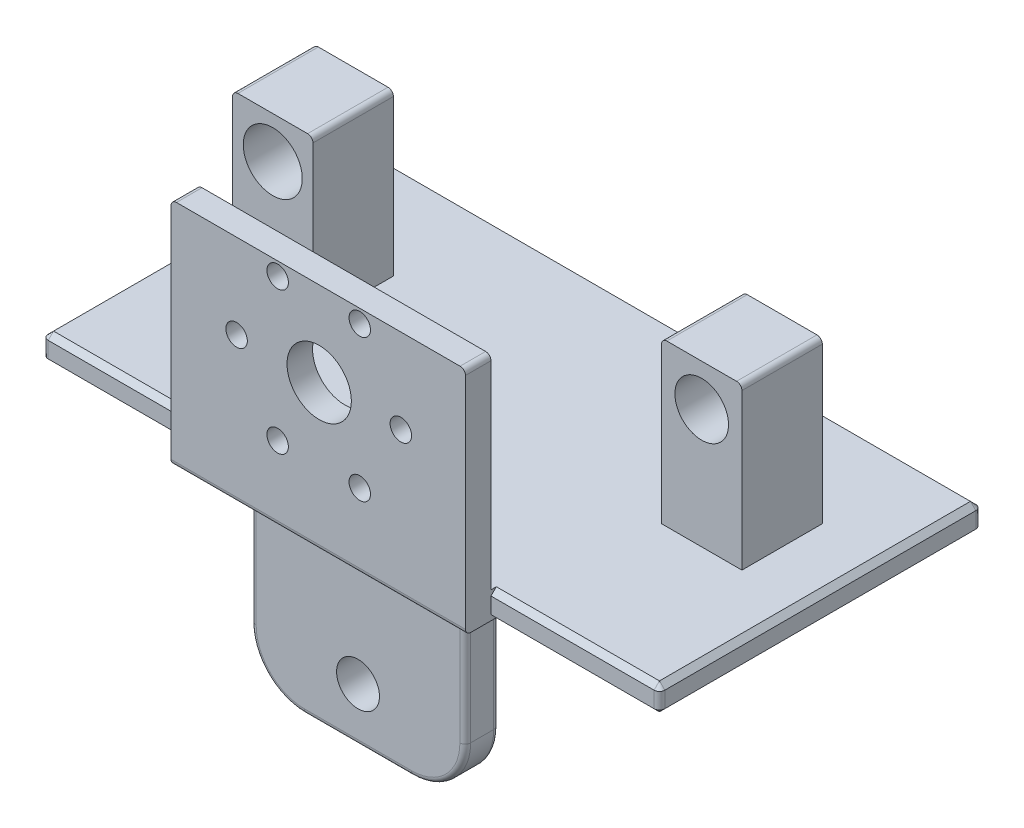
SolidWorks part; units mm, degrees
ref_plane "Alzado" through (0, 0, 0) normal (0, 0, 1) x (1, 0, 0)
ref_plane "Planta" through (0, 0, 0) normal (0, 1, 0) x (1, 0, 0)
ref_plane "Vista lateral" through (0, 0, 0) normal (1, 0, 0) x (0, 0, -1)
sketch "Croquis1" plane through (0, 0, 0) normal (0, 1, 0) x (1, 0, 0)
  line L0 (0, -17.4857) -> (43.5164, -17.4857) construction
  line L5 (75, -36.916) -> (-75, 36.916) construction
  line L6 (75, 36.916) -> (-75, -36.916) construction
  line L7 (43.5164, -17.4857) -> (43.5164, 12.5) construction
  line L8 (-30, 12.5) -> (-45, 12.5)
  line L9 (-30, 12.5) -> (-30, 27.5)
  line L10 (-30, 27.5) -> (-45, 27.5)
  line L11 (-45, 12.5) -> (-45, 27.5)
  line L12 (-30, 12.5) -> (-45, 27.5) construction
  line L13 (-30, 27.5) -> (-45, 12.5) construction
  line L14 (50, 12.5) -> (35, 12.5)
  line L15 (50, 12.5) -> (50, 27.5)
  line L16 (50, 27.5) -> (35, 27.5)
  line L17 (35, 12.5) -> (35, 27.5)
  line L18 (50, 12.5) -> (35, 27.5) construction
  line L19 (50, 27.5) -> (35, 12.5) construction
  point P0 (0, 0)
  point P7 (-37.5, 20)
  point P8 (42.5, 20)
  point P9 (0, 0)
  dimension "D1" = 150
  dimension "D2" = 80
  dimension "D3" = 15
  dimension "D4" = 15
  dimension "D5" = 15
  dimension "D6" = 15
  dimension "D7" = 29.9857
extrude "Saliente-Extruir1" add sketch "Croquis1" along normal blind 30
sketch "Croquis2" plane through (0, 0, -27.5) normal (0, 0, -1) x (-1, 0, 0)
  line L0 (30, 30) -> (30, 0) construction
  circle A0 centre (37.5, 22.2318) radius 5.5
  dimension "D1" = 11
  dimension "D2" = 7.5
extrude "Cortar-Extruir1" cut sketch "Croquis2" against normal blind 30
sketch "Croquis3" plane through (0, 0, -27.5) normal (0, 0, -1) x (-1, 0, 0)
  line L0 (37.5, 22.2318) -> (-42.5, 22.2318) construction
  circle A0 centre (-42.5, 22.2318) radius 5
  dimension "D1" = 10
extrude "Cortar-Extruir2" cut sketch "Croquis3" against normal blind 30
sketch "Croquis5" plane through (0, 0, 0) normal (0, 1, 0) x (1, 0, 0)
  line L5 (-45, 12.5) -> (-53.8007, -14.0809) construction
  line L6 (-53.8007, -14.0809) -> (-53.8007, 45.9191)
  line L7 (-53.8007, 45.9191) -> (61.1993, 45.9191)
  line L8 (61.1993, 45.9191) -> (61.1993, -14.0809)
  line L9 (61.1993, -14.0809) -> (-53.8007, -14.0809)
  dimension "D1" = 28
  dimension "D2" = 60
  dimension "D3" = 115
extrude "Saliente-Extruir3" add sketch "Croquis5" against normal blind 5
sketch "Croquis6" plane through (0, 0, 14.0809) normal (0, 0, 1) x (1, 0, 0)
  line L0 (-53.8007, -5) -> (61.1993, -5) construction
  line L1 (-25.119, -5) -> (29.7791, -5)
  line L2 (-25.119, -5) -> (-25.119, 38)
  line L3 (-25.119, 38) -> (29.7791, 38)
  line L4 (29.7791, -5) -> (29.7791, 38)
  dimension "D1" = 43
extrude "Saliente-Extruir4" add sketch "Croquis6" along normal blind 4.7625
ref_point "Punto1"
ref_axis "Eje1" through (2.3301, 16.5, 18.8434) along (0, 0, 1)
sketch "Croquis7" plane through (0, 0, 18.8434) normal (0, 0, 1) x (1, 0, 0)
  line L0 (-25.119, -5) -> (29.7791, -5) construction
  circle A0 centre (17.7301, 22.23) radius 2
  circle A2 centre (10.0719, 8.9656) radius 2
  circle A3 centre (-5.2445, 8.9656) radius 2
  circle A4 centre (-12.9027, 22.23) radius 2
  circle A5 centre (-5.2445, 35.4944) radius 2
  circle A6 centre (10.0719, 35.4944) radius 2
  point P5 (2.4137, 22.23)
  point P19 (2.4137, 22.23)
  dimension "D1" = 27.23
  dimension "D3" = 4
  dimension "D2" = 15.4
  dimension "D4" = 6
extrude "Cortar-Extruir3" cut sketch "Croquis7" against normal blind 4.7625
sketch "Croquis8" plane through (0, 0, 18.8434) normal (0, 0, 1) x (1, 0, 0)
  line L0 (-37.5, 22.2318) -> (42.5, 22.2318) construction
  circle A0 centre (2.5, 22.2318) radius 6
  dimension "D1" = 12
extrude "Cortar-Extruir4" cut sketch "Croquis8" against normal blind 10
sketch "Croquis9" plane through (0, -5, 0) normal (0, -1, 0) x (-1, 0, 0)
  line L0 (-2.6005, 12.6005) -> (-2.6005, 30.6005) construction
  line L5 (-2.6005, -5.3995) -> (-2.6005, 12.6005) construction
  line L9 (17.3995, 36.9005) -> (-22.6005, 36.9005)
  line L10 (17.3995, -5.3995) -> (-22.6005, -5.3995)
  line L11 (17.3995, -5.3995) -> (17.3995, -11.6995)
  line L12 (17.3995, -11.6995) -> (-22.6005, -11.6995)
  line L13 (-22.6005, -5.3995) -> (-22.6005, -11.6995)
  line L14 (-22.6005, 30.6005) -> (-22.6005, 36.9005)
  line L15 (17.3995, 30.6005) -> (-22.6005, 30.6005)
  line L16 (17.3995, 30.6005) -> (17.3995, 36.9005)
  point P11 (-2.6005, 12.6005)
  dimension "D1" = 40
  dimension "D2" = 40
  dimension "D3" = 18
  dimension "D4" = 6.3
  dimension "D5" = 6.3
  dimension "D6" = 18
extrude "Saliente-Extruir5" add sketch "Croquis9" along normal blind 35
fillet "Redondeo1" radius 10 4 edges at (22.6005, -40, -33.7505) (-17.3995, -40, -33.7505) (22.6005, -40, 8.5495) (-17.3995, -40, 8.5495)
sketch "Croquis10" plane through (0, 0, 11.6995) normal (0, 0, 1) x (1, 0, 0)
  line L0 (2.6005, -5) -> (2.6005, -30) construction
  line L1 (22.6005, -5) -> (-17.3995, -5) construction
  circle A0 centre (2.6005, -30) radius 4
  dimension "D1" = 8
  dimension "D2" = 25
extrude "Cortar-Extruir5" cut sketch "Croquis10" against normal up to surface (48.6 mm away) up to face at (2.6005, -25.6904, -36.9005)
fillet "Redondeo3" radius 1 20 edges at (-17.3995, -17.5, 11.6995) (-14.4706, -37.0711, 11.6995) (2.6005, -40, 11.6995) (19.6716, -37.0711, 11.6995) (22.6005, -17.5, 11.6995) (22.6005, -17.5, 5.3995) (19.6716, -37.0711, 5.3995) (2.6005, -40, 5.3995) (-14.4706, -37.0711, 5.3995) (-17.3995, -17.5, 5.3995) (-17.3995, -17.5, -30.6005) (-14.4706, -37.0711, -30.6005) (2.6005, -40, -30.6005) (19.6716, -37.0711, -30.6005) (22.6005, -17.5, -30.6005) (22.6005, -17.5, -36.9005) (-17.3995, -17.5, -36.9005) (-14.4706, -37.0711, -36.9005) (2.6005, -40, -36.9005) (19.6716, -37.0711, -36.9005)
fillet "Redondeo4" radius 1 4 edges at (61.1993, -2.5, 14.0809) (-53.8007, -2.5, 14.0809) (-53.8007, -2.5, -45.9191) (61.1993, -2.5, -45.9191)
fillet "Redondeo5" radius 1 4 edges at (-45, 30, -20) (-30, 30, -20) (35, 30, -20) (50, 30, -20)
fillet "Redondeo6" radius 1 2 edges at (-25.119, 38, 16.4622) (29.7791, 38, 16.4622)
fillet "Redondeo8" radius 1 1 edges at (2.3301, -5, 18.8434)
chamfer "Chaflán1" distance 1 angle 45 18 edges at (-38.9599, 0, 14.0809) (-53.5079, 0, 13.7881) (-53.8007, 0, -15.9191) (-53.5079, 0, -45.6262) (44.9892, 0, 14.0809) (3.6993, 0, -45.9191) (60.9064, 0, 13.7881) (60.9064, 0, -45.6262) (61.1993, 0, -15.9191) (44.9892, -5, 14.0809) (-38.9599, -5, 14.0809) (60.9064, -5, 13.7881) (-53.5079, -5, 13.7881) (61.1993, -5, -15.9191) (-53.8007, -5, -15.9191) (60.9064, -5, -45.6262) (-53.5079, -5, -45.6262) (3.6993, -5, -45.9191)
